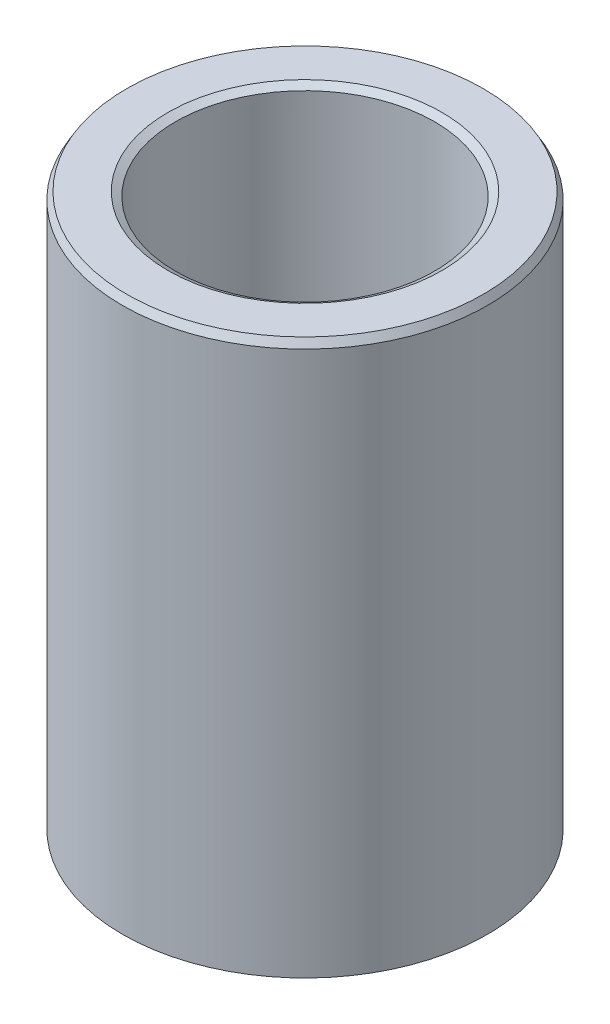
SolidWorks part; units mm, degrees
ref_plane "Front Plane" through (0, 0, 0) normal (0, 0, 1) x (1, 0, 0)
ref_plane "Top Plane" through (0, 0, 0) normal (0, 1, 0) x (1, 0, 0)
ref_plane "Right Plane" through (0, 0, 0) normal (1, 0, 0) x (0, 0, -1)
sketch "Sketch1" plane through (0, 0, 0) normal (0, 1, 0) x (1, 0, 0)
  circle A0 centre (0, 0) radius 20
  dimension "SLEEVE_OD" = 40
extrude "Boss-Extrude1" add sketch "Sketch1" along normal blind 60.96
sketch "Sketch2" plane through (0, 0, 0) normal (0, 1, 0) x (1, 0, 0)
  circle A0 centre (0, 0) radius 14.1923
  dimension "BORE_D" = 28.3847
extrude "Cut-Extrude1" cut sketch "Sketch2" along normal through all
chamfer "Chamfer1" distance 0.819 angle 30 4 edges at (0, 60.96, 14.1923) (0, 0, 14.1923) (0, 0, 20) (0, 60.96, 20) first distance on face at (0, 60.96, 14.1923) first distance on face at (0, 0, 14.1923) first distance on face at (0, 60.96, 20)
